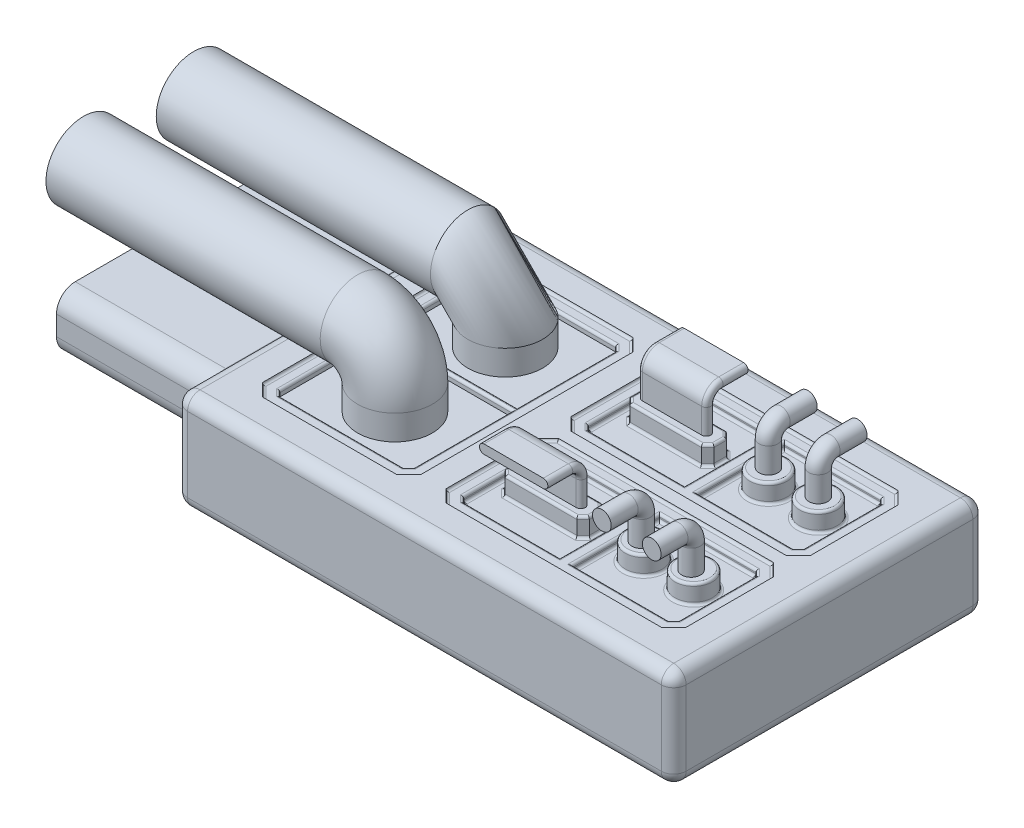
SolidWorks part; units mm, degrees
ref_plane "Front Plane" through (0, 0, 0) normal (0, 0, 1) x (1, 0, 0)
ref_plane "Top Plane" through (0, 0, 0) normal (0, 1, 0) x (1, 0, 0)
ref_plane "Right Plane" through (0, 0, 0) normal (1, 0, 0) x (0, 0, -1)
sketch "Sketch1" plane through (0, 0, 0) normal (0, 1, 0) x (1, 0, 0)
  line L1 (-200, 125) -> (200, 125)
  line L2 (-200, 125) -> (-200, -125)
  line L3 (-200, -125) -> (200, -125)
  line L4 (200, 125) -> (200, -125)
  line L5 (-200, 125) -> (200, -125) construction
  line L6 (-200, -125) -> (200, 125) construction
  point P0 (0, 0)
  dimension "D1" = 400
  dimension "D2" = 250
extrude "Boss-Extrude1" add sketch "Sketch1" along normal blind 80
fillet "Fillet1" radius 10 12 edges at (200, 80, 0) (200, 0, 0) (0, 80, 125) (200, 40, 125) (0, 0, 125) (200, 40, -125) (0, 80, -125) (0, 0, -125) (-200, 40, -125) (-200, 80, 0) (-200, 40, 125) (-200, 0, 0)
sketch "Sketch2" plane through (0, 80, 0) normal (0, 1, 0) x (1, 0, 0)
  line L0 (-22.5521, 85) -> (-12.5521, 95)
  line L1 (-160, 95) -> (-52.5521, 95)
  line L2 (-170, 85) -> (-170, -85)
  line L3 (-160, -95) -> (-52.5521, -95)
  line L4 (-42.5521, 85) -> (-42.5521, -85)
  line L5 (-12.5521, 95) -> (160, 95)
  line L6 (-22.5521, 85) -> (-22.5521, 15)
  line L7 (-12.5521, 5) -> (160, 5)
  line L8 (170, 85) -> (170, 15)
  line L9 (-12.5521, -5) -> (160, -5)
  line L10 (-22.5521, -15) -> (-22.5521, -85)
  line L11 (-12.5521, -95) -> (160, -95)
  line L12 (170, -15) -> (170, -85)
  line L13 (-22.5521, 15) -> (-12.5521, 5)
  line L14 (160, 5) -> (170, 15)
  line L15 (160, 95) -> (170, 85)
  line L16 (-22.5521, -15) -> (-12.5521, -5)
  line L17 (-22.5521, -85) -> (-12.5521, -95)
  line L18 (160, -95) -> (170, -85)
  line L19 (160, -5) -> (170, -15)
  line L20 (-170, 85) -> (-160, 95)
  line L21 (-52.5521, 95) -> (-42.5521, 85)
  line L22 (-170, -85) -> (-160, -95)
  line L23 (-52.5521, -95) -> (-42.5521, -85)
  line L24 (190, 115) -> (-190, 115) construction
  line L25 (-190, -115) -> (190, -115) construction
  line L26 (190, -115) -> (190, 115) construction
  line L27 (-190, 115) -> (-190, -115) construction
  line L28 (-160, 80.8579) -> (-160, 2)
  line L29 (-160, -80.8579) -> (-155.8579, -85)
  line L30 (-155.8579, -85) -> (-56.6942, -85)
  line L31 (-56.6942, -85) -> (-52.5521, -80.8579)
  line L32 (-52.5521, 80.8579) -> (-52.5521, 2)
  line L33 (-56.6942, 85) -> (-52.5521, 80.8579)
  line L34 (-155.8579, 85) -> (-56.6942, 85)
  line L35 (-160, 80.8579) -> (-155.8579, 85)
  line L36 (-12.5521, 80.8579) -> (-12.5521, 19.1421)
  line L37 (-12.5521, 19.1421) -> (-8.4099, 15)
  line L38 (-8.4099, 15) -> (68.724, 15)
  line L39 (155.8579, 15) -> (160, 19.1421)
  line L40 (160, 80.8579) -> (160, 19.1421)
  line L41 (155.8579, 85) -> (160, 80.8579)
  line L42 (-8.4099, 85) -> (68.724, 85)
  line L43 (-12.5521, 80.8579) -> (-8.4099, 85)
  line L44 (-12.5521, -19.1421) -> (-12.5521, -80.8579)
  line L45 (-12.5521, -80.8579) -> (-8.4099, -85)
  line L46 (-8.4099, -85) -> (68.724, -85)
  line L47 (155.8579, -85) -> (160, -80.8579)
  line L48 (160, -19.1421) -> (160, -80.8579)
  line L49 (155.8579, -15) -> (160, -19.1421)
  line L50 (-8.4099, -15) -> (68.724, -15)
  line L51 (-12.5521, -19.1421) -> (-8.4099, -15)
  line L52 (-160, -2) -> (-160, -80.8579)
  line L53 (-52.5521, 2) -> (-160, 2)
  line L54 (-52.5521, -2) -> (-160, -2)
  line L55 (-160, 80.8579) -> (-160, -80.8579) construction
  line L56 (-52.5521, -2) -> (-52.5521, -80.8579)
  line L57 (-52.5521, 80.8579) -> (-52.5521, -80.8579) construction
  line L58 (78.724, 15) -> (155.8579, 15)
  line L59 (68.724, 85) -> (68.724, 15)
  line L60 (78.724, -85) -> (155.8579, -85)
  line L61 (68.724, -15) -> (68.724, -85)
  line L62 (78.724, 85) -> (78.724, 15)
  line L63 (78.724, -15) -> (78.724, -85)
  line L64 (78.724, -15) -> (155.8579, -15)
  line L65 (78.724, 85) -> (155.8579, 85)
  line L66 (-8.4099, 85) -> (155.8579, 85) construction
  line L67 (-8.4099, 15) -> (155.8579, 15) construction
  line L69 (-8.4099, -15) -> (155.8579, -15) construction
  line L70 (-8.4099, -85) -> (155.8579, -85) construction
  point P0 (-170, 95)
  point P1 (-42.5521, -95)
  point P2 (-170, -95)
  point P3 (-42.5521, 95)
  point P4 (-22.5521, 95)
  point P5 (170, 5)
  point P6 (-22.5521, 5)
  point P7 (170, 95)
  point P8 (-22.5521, -5)
  point P9 (170, -95)
  point P10 (-22.5521, -95)
  point P11 (170, -5)
  dimension "D2" = 90
  dimension "D11" = 90
  dimension "D15" = 20
  dimension "D16" = 20
  dimension "D17" = 20
  dimension "D18" = 20
  dimension "D19" = 20
  dimension "D20" = 20
  dimension "D21" = 20
  dimension "D22" = 20
  dimension "D23" = 20
  dimension "D24" = 10
  dimension "D25" = 10
  dimension "D26" = 10
extrude "Cut-Extrude1" cut sketch "Sketch2" against normal blind 2 contours L1 L21 L4 L23 L3 L22 L2 L20 | L5 L15 L8 L14 L7 L13 L6 L0 | L9 L19 L12 L18 L11 L17 L10 L16
extrude "Cut-Extrude2" cut sketch "Sketch2<3>" against normal blind 5 from surface contours L56 L54 L52 L29 L30 L31 | L53 L32 L33 L34 L35 L28 | L59 L42 L43 L36 L37 L38 | L61 L50 L51 L44 L45 L46 | L65 L62 L58 L39 L40 L41 | L64 L63 L60 L47 L48 L49 region at (-106.276, 80, -43.4227) region at (-106.276, 80, 43.4227) region at (28.2047, 80, -50) region at (119.2432, 80, -50) region at (28.2047, 80, 50) region at (119.2432, 80, 50) starting at face at (-106.276, 78, 0)
sketch "Sketch2<3>" plane through (0, 80, 0) normal (0, 1, 0) x (1, 0, 0) same geometry as "Sketch2"
fillet "Fillet2" radius 2 60 edges at (73.724, 78, 5) (165, 78, 10) (170, 78, 50) (165, 78, 90) (73.724, 78, 95) (-17.5521, 78, 90) (-22.5521, 78, 50) (-17.5521, 78, 10) (117.2909, 78, 85) (157.9289, 78, 82.9289) (160, 78, 50) (157.9289, 78, 17.0711) (117.2909, 78, 15) (78.724, 78, 50) (68.724, 78, 50) (30.157, 78, 15) (-10.481, 78, 17.0711) (-12.5521, 78, 50) (-10.481, 78, 82.9289) (30.157, 78, 85) (73.724, 78, -95) (165, 78, -90) (170, 78, -50) (165, 78, -10) (73.724, 78, -5) (-17.5521, 78, -10) (-22.5521, 78, -50) (-17.5521, 78, -90) (117.2909, 78, -15) (157.9289, 78, -17.0711) (160, 78, -50) (157.9289, 78, -82.9289) (117.2909, 78, -85) (78.724, 78, -50) (68.724, 78, -50) (30.157, 78, -85) (-10.481, 78, -82.9289) (-12.5521, 78, -50) (-10.481, 78, -17.0711) (30.157, 78, -15) (-106.276, 78, -95) (-47.5521, 78, -90) (-42.5521, 78, 0) (-47.5521, 78, 90) (-106.276, 78, 95) (-165, 78, 90) (-170, 78, 0) (-165, 78, -90) (-160, 78, 41.4289) (-157.9289, 78, 82.9289) (-106.276, 78, 85) (-54.6231, 78, 82.9289) (-52.5521, 78, 41.4289) (-106.276, 78, 2) (-52.5521, 78, -41.4289) (-54.6231, 78, -82.9289) (-106.276, 78, -85) (-157.9289, 78, -82.9289) (-160, 78, -41.4289) (-106.276, 78, -2)
sketch "Sketch3" plane through (0, 73, 0) normal (0, 1, 0) x (1, 0, 0)
  line L0 (-124.5984, 44.4386) -> (-84.5984, 44.4386) construction
  line L1 (-124.5984, 70.4624) -> (-84.5984, 70.4624)
  line L2 (-124.5984, 18.4148) -> (-84.5984, 18.4148)
  line L3 (-123.76, -44.8578) -> (-83.76, -44.8578) construction
  line L4 (-123.76, -18.8341) -> (-83.76, -18.8341)
  line L5 (-123.76, -70.8816) -> (-83.76, -70.8816)
  line L6 (160, 19.1421) -> (160, 80.8579) construction
  line L7 (160, -80.8579) -> (160, -19.1421) construction
  line L8 (-5.2404, 55) -> (-0.2404, 60)
  line L9 (140, -49) -> (100, -49) construction
  line L10 (100, 51) -> (140, 51) construction
  line L11 (155.8579, 85) -> (78.724, 85) construction
  line L12 (155.8579, -15) -> (78.724, -15) construction
  line L13 (68.724, 85) -> (-8.4099, 85) construction
  line L14 (-0.2404, 60) -> (57.2596, 60)
  line L15 (-5.2404, 55) -> (-5.2404, 45)
  line L16 (-0.2404, 40) -> (57.2596, 40)
  line L17 (62.2596, 55) -> (62.2596, 45)
  line L18 (-0.2404, -40) -> (57.2596, -40)
  line L19 (-5.2404, -45) -> (-5.2404, -55)
  line L20 (-0.2404, -60) -> (57.2596, -60)
  line L21 (62.2596, -45) -> (62.2596, -55)
  line L22 (68.724, -85) -> (-8.4099, -85) construction
  line L23 (57.2596, 60) -> (62.2596, 55)
  line L24 (57.2596, 40) -> (62.2596, 45)
  line L25 (-5.2404, 45) -> (-0.2404, 40)
  line L26 (-5.2404, -45) -> (-0.2404, -40)
  line L27 (57.2596, -40) -> (62.2596, -45)
  line L28 (57.2596, -60) -> (62.2596, -55)
  line L29 (-5.2404, -55) -> (-0.2404, -60)
  line L30 (12.5137, 46.6276) -> (9.515, 46.6276)
  line L33 (0, 0) -> (28.5096, 0) construction
  line L36 (8.9416, 52.2123) -> (13.087, 52.2123)
  line L38 (44.5137, 46.6276) -> (41.515, 46.6276)
  line L39 (16.9416, 52.2123) -> (21.087, 52.2123)
  line L40 (32.9416, -52.2123) -> (37.087, -52.2123)
  line L41 (24.9416, 52.2123) -> (29.087, 52.2123)
  line L42 (20.5137, 46.6276) -> (17.515, 46.6276)
  line L43 (24.9416, -52.2123) -> (29.087, -52.2123)
  line L44 (32.9416, 52.2123) -> (37.087, 52.2123)
  line L45 (28.5137, 46.6276) -> (25.515, 46.6276)
  line L46 (40.9416, 52.2123) -> (45.087, 52.2123)
  line L47 (36.5137, 46.6276) -> (33.515, 46.6276)
  line L48 (16.9416, -52.2123) -> (21.087, -52.2123)
  line L49 (8.9416, -52.2123) -> (13.087, -52.2123)
  line L50 (12.5137, -46.6276) -> (9.515, -46.6276)
  line L51 (20.5137, -46.6276) -> (17.515, -46.6276)
  line L52 (28.5137, -46.6276) -> (25.515, -46.6276)
  line L53 (36.5137, -46.6276) -> (33.515, -46.6276)
  line L54 (44.5137, -46.6276) -> (41.515, -46.6276)
  line L55 (40.9416, -52.2123) -> (45.087, -52.2123)
  arc A0 (-124.5984, 70.4624) -> (-124.5984, 18.4148) centre (-124.5984, 44.4386) ccw
  arc A1 (-84.5984, 18.4148) -> (-84.5984, 70.4624) centre (-84.5984, 44.4386) ccw
  arc A2 (-123.76, -18.8341) -> (-123.76, -70.8816) centre (-123.76, -44.8578) ccw
  arc A3 (-83.76, -70.8816) -> (-83.76, -18.8341) centre (-83.76, -44.8578) ccw
  circle A4 centre (100, 51) radius 15
  circle A5 centre (140, 51) radius 15
  circle A6 centre (100, -49) radius 15
  circle A7 centre (140, -49) radius 15
  circle A8 centre (100, 51) radius 10.6
  circle A9 centre (140, 51) radius 10.6
  circle A10 centre (100, -49) radius 10.6
  circle A11 centre (140, -49) radius 10.6
  arc A12 (7.0143, 52.775) -> (7.0143, 45.6104) centre (7.0143, 49.1927) ccw
  arc A16 (8.9416, 52.2123) -> (9.515, 46.6276) centre (7.0143, 49.1927) ccw
  arc A17 (12.5137, 46.6276) -> (17.515, 46.6276) centre (15.0143, 49.1927) ccw
  arc A18 (20.5137, 46.6276) -> (25.515, 46.6276) centre (23.0143, 49.1927) ccw
  arc A19 (28.5137, 46.6276) -> (33.515, 46.6276) centre (31.0143, 49.1927) ccw
  arc A20 (36.5137, 46.6276) -> (41.515, 46.6276) centre (39.0143, 49.1927) ccw
  arc A21 (44.5137, 46.6276) -> (45.087, 52.2123) centre (47.0143, 49.1927) ccw
  arc A23 (40.9416, -52.2123) -> (37.087, -52.2123) centre (39.0143, -49.1927) cw
  circle A24 centre (55.0143, 49.1927) radius 3.5823 [skipped]
  arc A25 (16.9416, 52.2123) -> (13.087, 52.2123) centre (15.0143, 49.1927) ccw
  arc A26 (24.9416, 52.2123) -> (21.087, 52.2123) centre (23.0143, 49.1927) ccw
  arc A27 (32.9416, 52.2123) -> (29.087, 52.2123) centre (31.0143, 49.1927) ccw
  arc A28 (40.9416, 52.2123) -> (37.087, 52.2123) centre (39.0143, 49.1927) ccw
  arc A29 (32.9416, -52.2123) -> (29.087, -52.2123) centre (31.0143, -49.1927) cw
  arc A30 (24.9416, -52.2123) -> (21.087, -52.2123) centre (23.0143, -49.1927) cw
  arc A31 (16.9416, -52.2123) -> (13.087, -52.2123) centre (15.0143, -49.1927) cw
  arc A32 (8.9416, -52.2123) -> (9.515, -46.6276) centre (7.0143, -49.1927) cw
  arc A33 (12.5137, -46.6276) -> (17.515, -46.6276) centre (15.0143, -49.1927) cw
  arc A34 (20.5137, -46.6276) -> (25.515, -46.6276) centre (23.0143, -49.1927) cw
  arc A35 (28.5137, -46.6276) -> (33.515, -46.6276) centre (31.0143, -49.1927) cw
  arc A36 (36.5137, -46.6276) -> (41.515, -46.6276) centre (39.0143, -49.1927) cw
  arc A37 (44.5137, -46.6276) -> (45.087, -52.2123) centre (47.0143, -49.1927) cw
  point P2 (-104.5984, 44.4386)
  point P10 (-103.76, -44.8578)
  point P34 (-5.2404, 60)
  point P35 (62.2596, 40)
  point P36 (-5.2404, 40)
  point P37 (62.2596, 60)
  point P38 (-5.2404, -40)
  point P39 (62.2596, -60)
  point P40 (-5.2404, -60)
  point P41 (62.2596, -40)
  point P64 (29.5143, 49.1927)
  dimension "D2" = 30
  dimension "D9" = 21.2
  dimension "D1" = 40
  dimension "D3" = 40
  dimension "D4" = 20
  dimension "D5" = 20
  dimension "D6" = 40
  dimension "D7" = 34
  dimension "D8" = 34
  dimension "D10" = 20
  dimension "D11" = 20
  dimension "D12" = 67.5
  dimension "D13" = 67.5
  dimension "D14" = 25
  dimension "D15" = 25
  dimension "D17" = 7
extrude "Boss-Extrude2" add sketch "Sketch3" along normal blind 15 contours L16 L24 L17 L23 L14 L8 L15 L25 | L18 L27 L21 L28 L20 L29 L19 L26 | A4 | A5 | A6 | A7
fillet "Fillet3" radius 2 60 edges at (-5.2404, 88, -50) (-2.7404, 88, -57.5) (28.5096, 88, -60) (59.7596, 88, -57.5) (62.2596, 88, -50) (59.7596, 88, -42.5) (28.5096, 88, -40) (-2.7404, 88, -42.5) (28.5096, 88, 40) (59.7596, 88, 42.5) (62.2596, 88, 50) (59.7596, 88, 57.5) (28.5096, 88, 60) (-2.7404, 88, 57.5) (-5.2404, 88, 50) (-2.7404, 88, 42.5) (157.9289, 73, 17.0711) (160, 73, 50) (157.9289, 73, 82.9289) (117.2909, 73, 85) (78.724, 73, 50) (117.2909, 73, 15) (100, 73, 34) (140, 73, 34) (-12.5521, 73, 50) (-10.481, 73, 17.0711) (30.157, 73, 15) (68.724, 73, 50) (30.157, 73, 85) (-10.481, 73, 82.9289) (-5.2404, 73, 50) (-2.7404, 73, 57.5) (28.5096, 73, 60) (59.7596, 73, 57.5) (62.2596, 73, 50) (59.7596, 73, 42.5) (28.5096, 73, 40) (-2.7404, 73, 42.5) (157.9289, 73, -82.9289) (160, 73, -50) (157.9289, 73, -17.0711) (117.2909, 73, -15) (78.724, 73, -50) (117.2909, 73, -85) (100, 73, -66) (140, 73, -66) (59.7596, 73, -42.5) (62.2596, 73, -50) (59.7596, 73, -57.5) (28.5096, 73, -60) (-2.7404, 73, -57.5) (-5.2404, 73, -50) (-2.7404, 73, -42.5) (28.5096, 73, -40) (-12.5521, 73, -50) (-10.481, 73, -82.9289) (30.157, 73, -85) (68.724, 73, -50) (30.157, 73, -15) (-10.481, 73, -17.0711)
fillet "Fillet4" radius 2 4 edges at (140, 88, 64) (100, 88, 64) (140, 88, -36) (100, 88, -36)
sketch "Sketch4" plane through (200, 0, 0) normal (1, 0, 0) x (0, 0, -1)
  line L1 (-73.1698, 63.1828) -> (73.1698, 63.1828)
  line L2 (-88.1698, 48.1828) -> (-88.1698, 32.4806)
  line L3 (-73.1698, 17.4806) -> (73.1698, 17.4806)
  line L4 (88.1698, 48.1828) -> (88.1698, 32.4806)
  line L5 (-88.1698, 63.1828) -> (88.1698, 17.4806) construction
  line L6 (-88.1698, 17.4806) -> (88.1698, 63.1828) construction
  arc A0 (73.1698, 63.1828) -> (88.1698, 48.1828) centre (73.1698, 48.1828) cw
  arc A1 (73.1698, 17.4806) -> (88.1698, 32.4806) centre (73.1698, 32.4806) ccw
  arc A2 (-88.1698, 32.4806) -> (-73.1698, 17.4806) centre (-73.1698, 32.4806) ccw
  arc A3 (-73.1698, 63.1828) -> (-88.1698, 48.1828) centre (-73.1698, 48.1828) ccw
  point P0 (0, 40.3317)
  point P17 (0, 40.3317)
  dimension "D1" = 15
extrude "Boss-Extrude3" add sketch "Sketch4" against normal blind 132 from surface starting at face at (-200, 40, 0)
fillet "Fillet6" radius 12 8 edges at (-200, 63.1828, 0) (-200, 58.7894, -83.7764) (-200, 40.3317, -88.1698) (-200, 21.874, -83.7764) (-200, 17.4806, 0) (-200, 21.874, 83.7764) (-200, 40.3317, 88.1698) (-200, 58.7894, 83.7764)
sketch3d "3DSketch1"
  line L0 (-103.76, 73, 44.8578) -> (-103.76, 93, 44.8578)
  line L1 (-133.76, 123, 44.8578) -> (-353.76, 123, 44.8578)
  arc A0 (-103.76, 93, 44.8578) -> (-133.76, 123, 44.8578) centre (-133.76, 93, 44.8578) ccw
  point P6 (-103.76, 123, 44.8578)
  point P7 (-133.76, 93, 74.8578)
  point P8 (-416.8152, 143, 44.8578)
  dimension "D2" = 30
  dimension "D1" = 50
  dimension "D3" = 250
sweep "Sweep1" add path "3DSketch1" circular profile diameter 60 parameters "D3"=60
sketch3d "3DSketch2"
  line L0 (-104.5984, 73, -44.4386) -> (-104.5984, 93, -44.4386)
  line L1 (-134.5984, 123, -44.4386) -> (-354.5984, 123, -44.4386)
  arc A0 (-104.5984, 93, -44.4386) -> (-134.5984, 123, -44.4386) centre (-134.5984, 93, -44.4386) ccw
  point P6 (-104.5984, 123, -44.4386)
  point P7 (-134.5984, 93, -14.4386)
  dimension "D3" = 30
  dimension "D1" = 50
  dimension "D2" = 250
sweep "Sweep2" add path "3DSketch2" circular profile diameter 60 parameters "D3"=60
sketch "Sketch47" plane through (0, 88, 0) normal (0, 1, 0) x (1, 0, 0)
  line L20 (3.0925, 50.3346) -> (50.7276, 50.3346) construction
  line L31 (3.0925, 53.9625) -> (50.7276, 53.9625)
  line L32 (3.0925, 46.7068) -> (50.7276, 46.7068)
  arc A21 (3.0925, 53.9625) -> (3.0925, 46.7068) centre (3.0925, 50.3346) ccw
  arc A32 (50.7276, 46.7068) -> (50.7276, 53.9625) centre (50.7276, 50.3346) ccw
  point P2 (26.9101, 50.3346)
sketch3d "3DSketch3"
  line L0 (26.9101, 88, -50.3346) -> (26.9101, 108, -50.3346)
  line L1 (26.9101, 118, -60.3346) -> (26.9101, 118, -80.3346)
  arc A0 (26.9101, 118, -60.3346) -> (26.9101, 108, -50.3346) centre (26.9101, 108, -60.3346) ccw
  point P6 (26.9101, 118, -50.3346)
  point P7 (36.9101, 108, -60.3346)
  point P8 (23.0143, 88, -49.1927)
  point P9 (26.9101, 88, -50.3346)
  dimension "D3" = 10
  dimension "D1" = 30
  dimension "D2" = 30
sweep "Sweep4" add profiles "Sketch47" path "3DSketch3"
sketch3d "3DSketch4"
  line L0 (100, 88, -51) -> (100, 108.2059, -51)
  line L1 (100, 77.5053, -51) -> (100, 102.9894, -51) construction
  line L2 (100, 118.2059, -61) -> (100, 118.2059, -82.6444)
  arc A0 (100, 108.2059, -51) -> (100, 118.2059, -61) centre (100, 108.2059, -61) ccw
  point P7 (100, 118.2059, -51)
  point P8 (90, 108.2059, -61)
  point P9 (100, 118.2059, -82.6444)
  dimension "D1" = 10
sweep "Sweep5" add path "3DSketch4" circular profile diameter 15 parameters "D3"=15
pattern_linear "LPattern1" count 2 spacing 40 along (1, 0, 0) of "Sweep5"
mirror "Mirror1" about plane through (0, 0, 0) normal (0, 0, 1) of "LPattern1", "Sweep5", "Sweep4"
